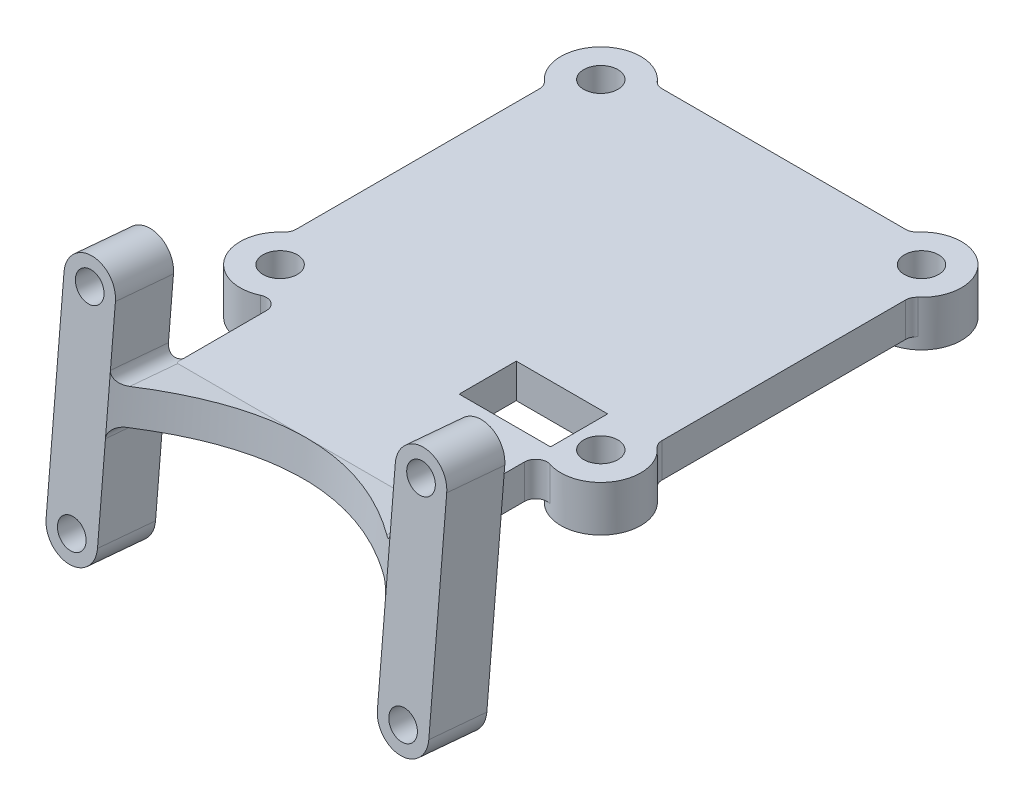
SolidWorks part; units mm, degrees
ref_plane "Front Plane" through (0, 0, 0) normal (0, 0, 1) x (1, 0, 0)
ref_plane "Top Plane" through (0, 0, 0) normal (0, 1, 0) x (1, 0, 0)
ref_plane "Right Plane" through (0, 0, 0) normal (1, 0, 0) x (0, 0, -1)
sketch "Sketch1" plane through (0, 0, 0) normal (0, 1, 0) x (1, 0, 0)
  line L0 (-16.0143, 16.0143) -> (-16.0143, 11.1488) construction
  line L1 (11.1488, 16.0143) -> (-11.1488, 16.0143)
  line L2 (16.0143, 11.1488) -> (16.0143, -11.1488)
  line L4 (-16.0143, 11.1488) -> (-16.0143, -11.1488)
  line L5 (16.0143, 16.0143) -> (-16.0143, -16.0143) construction
  line L6 (15.9857, -15.9857) -> (-16.0143, 16.0143) construction
  line L7 (-16.0143, 16.0143) -> (-11.1488, 16.0143) construction
  line L8 (16.0143, 16.0143) -> (16.0143, 11.0332) construction
  line L9 (16.0143, 16.0143) -> (11.1488, 16.0143) construction
  line L10 (15.9857, -15.9857) -> (11.6143, -15.9857) construction
  line L11 (15.9857, -15.9857) -> (16.0143, -11.1488) construction
  line L12 (-16.0143, -16.0143) -> (-16.0143, -11.1488) construction
  line L15 (11.6143, -11.0143) -> (3.6143, -11.0143)
  line L16 (11.6143, -11.0143) -> (11.6143, -15.9857)
  line L18 (3.6143, -11.0143) -> (3.6143, -16.0143)
  line L19 (11.6143, -11.0143) -> (3.6143, -16.0143) construction
  line L20 (11.6143, -15.9857) -> (3.6143, -11.0143) construction
  line L21 (11.6143, -15.9857) -> (11.6143, -16.0143)
  line L22 (-11.1488, -26.0143) -> (11.6143, -26.0143)
  line L23 (-11.1488, -26.0143) -> (-11.1488, -16.0143)
  line L24 (3.6143, -16.0143) -> (11.6143, -16.0143)
  line L25 (11.6143, -26.0143) -> (11.6143, -16.5629)
  line L26 (-11.1488, -26.0143) -> (11.6143, -16.0143) construction
  line L27 (-11.1488, -16.0143) -> (11.6143, -26.0143) construction
  circle A0 centre (14.0361, 14.0361) radius 1.5
  circle A1 centre (14.0361, -14.0361) radius 1.5
  circle A2 centre (-14.0361, -14.0361) radius 1.5
  circle A3 centre (-14.0361, 14.0361) radius 1.5
  arc A4 (-11.1488, 16.0143) -> (-16.0143, 11.1488) centre (-14.0361, 14.0361) ccw
  arc A5 (16.0143, 11.1488) -> (11.1488, 16.0143) centre (14.0361, 14.0361) ccw
  arc A6 (11.6143, -16.5629) -> (16.0143, -11.1488) centre (14.0361, -14.0361) ccw
  arc A7 (-16.0143, -11.1488) -> (-11.1488, -16.0143) centre (-14.0361, -14.0361) ccw
  point P0 (0, 0)
  point P3 (0.2328, -21.0143)
  point P8 (-12.9754, -12.9754)
  point P9 (12.9754, 12.9754)
  point P20 (7.6258, -13.5071)
  point P31 (0, 0)
  point P51 (0, 0)
  dimension "D3" = 3
  dimension "D5" = 2
  dimension "D7" = 10
  dimension "D1" = 32
  dimension "D4" = 36.7
  dimension "D8" = 12.4
  dimension "D9" = 8
  dimension "D10" = 5
  dimension "D2" = 45.2953
  dimension "D6" = 4
extrude "Boss-Extrude1" add sketch "Sketch1" along normal blind 2.9967
ref_plane "Plane1" through (0.2328, 0, 0) normal (1, 0, 0) x (0, 0, -1)
sketch "Sketch4" plane through (0, 0, 0) normal (0, -1, 0) x (1, 0, 0)
  line L3 (11.6143, 11.5092) -> (11.6143, 16.5629)
  circle A0 centre (-14.0361, -14.0361) radius 1.5 construction
  circle A1 centre (14.0361, -14.0361) radius 1.5 construction
  circle A2 centre (14.0361, 14.0361) radius 1.5 construction
  circle A3 centre (-14.0361, 14.0361) radius 1.5 construction
  circle A4 centre (-14.0361, -14.0361) radius 1.5
  circle A5 centre (14.0361, -14.0361) radius 1.5
  circle A6 centre (14.0361, 14.0361) radius 1.5
  circle A7 centre (-14.0361, 14.0361) radius 1.5
  circle A8 centre (-14.0361, 14.0361) radius 3.5
  arc A9 (11.6143, 11.5092) -> (11.6143, 16.5629) centre (14.0361, 14.0361) ccw
  circle A10 centre (14.0361, -14.0361) radius 3.5
  circle A11 centre (-14.0361, -14.0361) radius 3.5
extrude "Boss-Extrude3" add sketch "Sketch4" along normal blind 1
ref_plane "Plane3" through (0, 2.2814, 26.0769) normal (0, 0.0872, 0.9962) x (1, 0, 0)
sketch "Sketch7" plane through (0, 2.2814, 26.0769) normal (0, 0.0872, 0.9962) x (1, 0, 0)
  line L0 (0.2328, 5.9839) -> (0.2328, -10.5185) construction
  line L1 (0.2328, -2.2673) -> (-16.5172, -2.2673) construction
  line L2 (-12.0172, 6.7327) -> (-12.0172, 0.718)
  line L3 (-16.5172, 6.7327) -> (-16.5172, -11.2673)
  line L4 (12.4828, 6.7327) -> (12.4828, 0.718)
  line L5 (16.9828, 6.7327) -> (16.9828, -11.2673)
  line L6 (-11.1488, -2.2673) -> (11.6143, -2.2673) construction
  line L7 (-12.0172, -2.2673) -> (12.4828, -2.2673)
  line L8 (-12.0172, 0.718) -> (12.4828, 0.718)
  line L9 (12.4828, -2.2673) -> (12.4828, -11.2673)
  line L10 (-12.0172, -2.2673) -> (-12.0172, -11.2673)
  line L11 (-11.1488, 0.718) -> (11.6143, 0.718) construction
  line L12 (0.2328, -1.6482) -> (0.2328, 1.6482) construction
  circle A0 centre (-14.2672, 6.7327) radius 1.25
  arc A1 (-12.0172, 6.7327) -> (-16.5172, 6.7327) centre (-14.2672, 6.7327) ccw
  circle A2 centre (-14.2672, -11.2673) radius 1.25
  arc A3 (-12.0172, -11.2673) -> (-16.5172, -11.2673) centre (-14.2672, -11.2673) cw
  circle A4 centre (14.7328, -11.2673) radius 1.25
  arc A5 (12.4828, 6.7327) -> (16.9828, 6.7327) centre (14.7328, 6.7327) cw
  arc A6 (12.4828, -11.2673) -> (16.9828, -11.2673) centre (14.7328, -11.2673) ccw
  circle A7 centre (14.7328, 6.7327) radius 1.25
  point P10 (-16.5172, -2.2673)
  point P15 (-12.25, -2.2673)
  dimension "D1" = 2.5
  dimension "D2" = 1
  dimension "D3" = 29
  dimension "D4" = 18
extrude "Boss-Extrude5" add sketch "Sketch7" along normal blind 5 and the other way blind 0.1
sketch "Sketch9" plane through (0, -2.2587, 0.1976) normal (0, -0.9962, 0.0872) x (1, 0, 0)
  line L0 (-9.7672, 31.1765) -> (-9.7672, 26.1765) construction
  line L1 (-12.0172, 31.1765) -> (12.4828, 31.1765) construction
  line L2 (-9.7672, 26.1765) -> (10.2328, 26.1765) construction
  line L3 (0.2328, 26.1765) -> (0.2328, 31.1765) construction
  line L4 (10.2328, 31.1765) -> (10.2328, 26.1765) construction
  line L5 (-9.7672, 31.1765) -> (10.2328, 31.1765) construction
  line L6 (-12.0172, 31.1765) -> (12.4828, 31.1765)
  spline S0 degree 2 poles (-12.0172, 31.1765) (0.2328, 21.1765) (12.4828, 31.1765) knots 0 0 0 1 1 1
  dimension "D1" = 5
  dimension "D2" = 20
extrude "Cut-Extrude4" cut sketch "Sketch9" against normal through all both and the other way through all
fillet "Fillet3" radius 0.8 2 edges at (-11.1488, 2.4186, 25.9645) (11.6143, 2.4186, 25.9645)
fillet "Fillet4" radius 1 12 edges at (-16.0143, 1.4983, 11.1488) (-16.0143, 1.4983, -11.1488) (11.1488, 1.4983, -16.0143) (16.0143, 1.4983, -11.1488) (-11.1488, 1.4983, -16.0143) (16.0143, 1.4983, 11.1488) (11.6143, 1.4983, 16.5629) (-11.1488, 1.4983, 16.0143) (12.4828, 3.2102, 28.455) (-12.0172, 3.2102, 28.455) (12.4828, 0.2363, 28.7152) (-12.0172, 0.2363, 28.7152)
